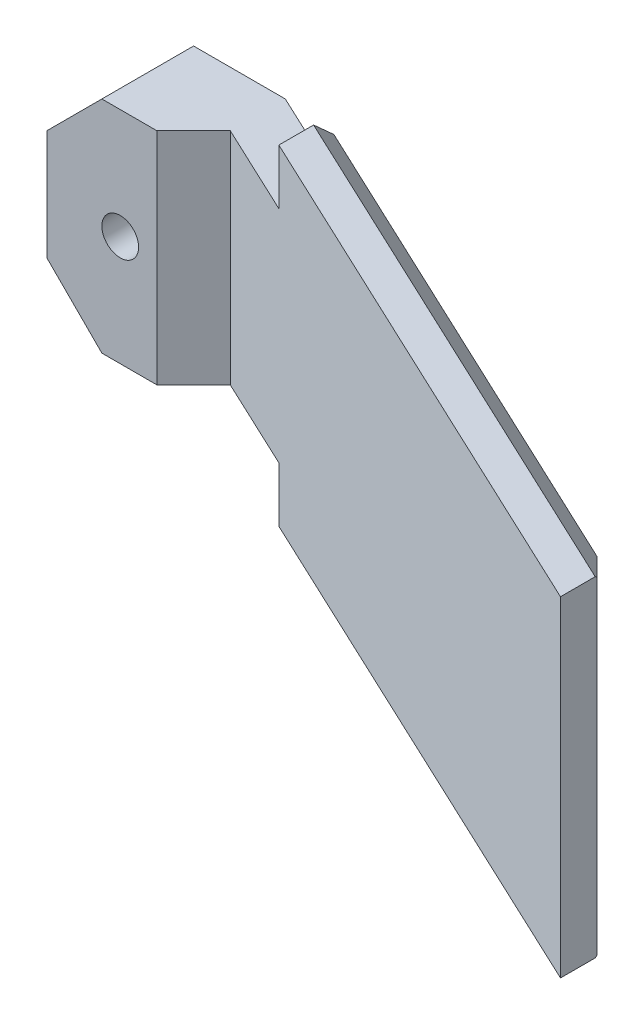
SolidWorks part; units mm, degrees
ref_plane "Alzado" through (0, 0, 0) normal (0, 0, 1) x (1, 0, 0)
ref_plane "Planta" through (0, 0, 0) normal (0, 1, 0) x (1, 0, 0)
ref_plane "Vista lateral" through (0, 0, 0) normal (1, 0, 0) x (0, 0, -1)
sketch "Croquis1" plane through (0, 0, 0) normal (0, 1, 0) x (1, 0, 0)
  line L0 (4, -1.5) -> (38, -17.5)
  line L1 (-4, -1.5) -> (4, -1.5)
  line L2 (-4, -1.5) -> (-4, 1.5)
  line L3 (-4, 1.5) -> (4, 1.5)
  line L5 (-4, -1.5) -> (4, 1.5) construction
  line L6 (-4, 1.5) -> (4, -1.5) construction
  line L7 (4, 1.5) -> (38, -14.5)
  line L8 (38, -14.5) -> (38, -17.5)
  point P0 (0, 0)
  dimension "D1" = 3
  dimension "D2" = 3
  dimension "D3" = 8
  dimension "D4" = 16
  dimension "D5" = 34
extrude "Saliente-Extruir1" add sketch "Croquis1" along normal blind 18
sketch "Croquis2" plane through (0, 0, -1.5) normal (0, 0, -1) x (-1, 0, 0)
  line L0 (4, 9) -> (-5.3709, 9) construction
  line L1 (4, 18) -> (4, 0) construction
  line L2 (0, 18) -> (0, 0) construction
  line L3 (-4, 18) -> (4, 18) construction
  circle A0 centre (0, 9) radius 2.5
  dimension "D1" = 5
extrude "Cortar-Extruir1" cut sketch "Croquis2" against normal blind 2.5
sketch "Croquis3" plane through (0, 0, -1.5) normal (0, 0, -1) x (-1, 0, 0)
  line L1 (4, 18) -> (-9, 18)
  line L2 (4, 18) -> (4, 15)
  line L3 (4, 15) -> (-9, 15)
  line L4 (-9, 18) -> (-9, 15)
  line L5 (4, 0) -> (-9, 0)
  line L6 (4, 0) -> (4, 3)
  line L7 (4, 3) -> (-9, 3)
  line L8 (-9, 0) -> (-9, 3)
  dimension "D1" = 3
  dimension "D2" = 3
  dimension "D3" = 13
extrude "Cortar-Extruir2" cut sketch "Croquis3" against normal through all
chamfer "Chaflán1" distance 1 angle 45 2 edges at (23.5, 0, 7.6765) (23.5, 18, 7.6765)
chamfer "Chaflán2" distance 1 angle 45 1 edges at (38, 9, 14.5) first distance on face at (38, 9, 15.8684)
sketch "Croquis4" plane through (0, 0, 1.5) normal (0, 0, 1) x (1, 0, 0)
  line L1 (4, 15) -> (-4, 15)
  line L2 (4, 15) -> (4, 3)
  line L3 (4, 3) -> (-4, 3)
  line L4 (-4, 15) -> (-4, 3)
extrude "Saliente-Extruir2" add sketch "Croquis4" along normal blind 2
sketch "Croquis5" plane through (0, 0, 1) normal (0, 0, -1) x (-1, 0, 0)
  circle A0 centre (0, 9) radius 1
  dimension "D1" = 2
extrude "Cortar-Extruir3" cut sketch "Croquis5" against normal through all
chamfer "Chaflán3" distance 3 angle 45 2 edges at (-4, 15, 1) (-4, 3, 1)
chamfer "Chaflán4" distance 2 angle 45 1 edges at (4, 9, 3.5)
